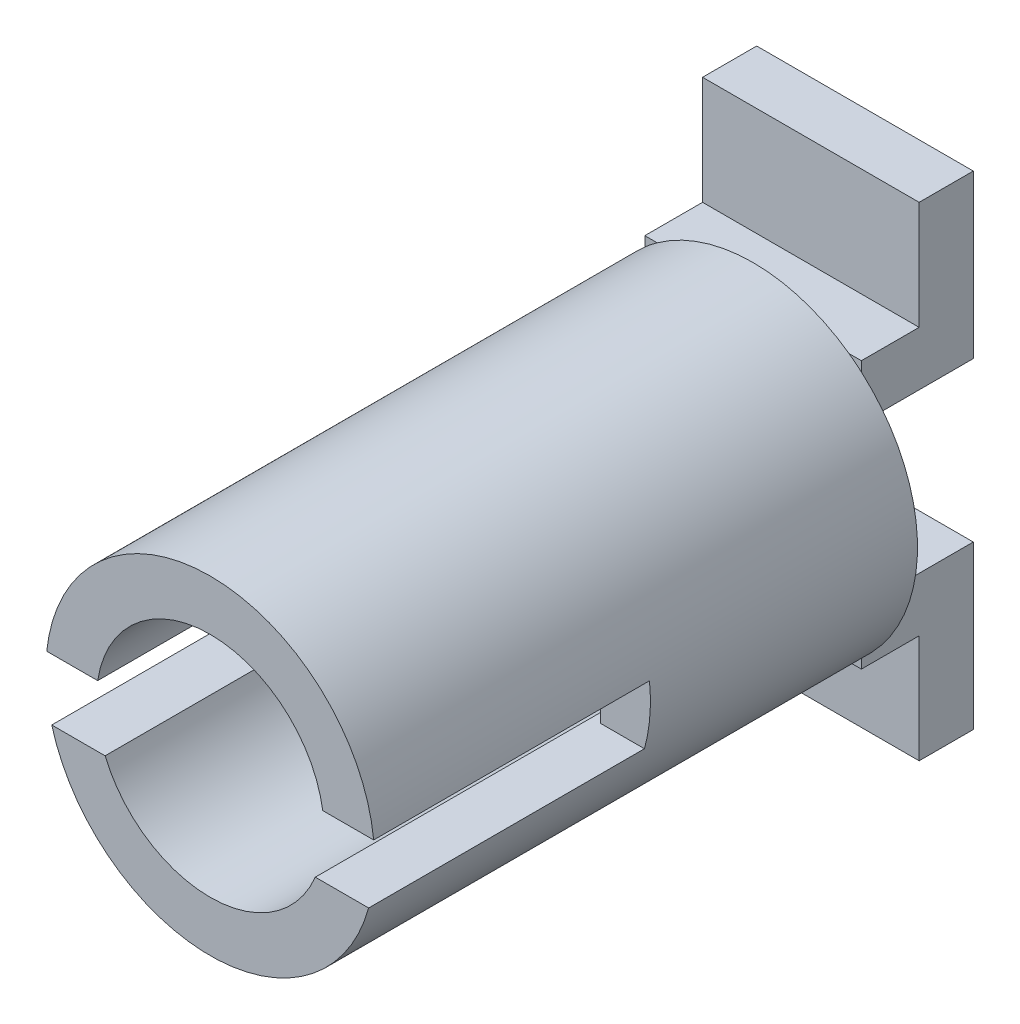
SolidWorks part; units mm, degrees
ref_plane "Front Plane" through (0, 0, 0) normal (0, 0, 1) x (1, 0, 0)
ref_plane "Top Plane" through (0, 0, 0) normal (0, 1, 0) x (1, 0, 0)
ref_plane "Right Plane" through (0, 0, 0) normal (1, 0, 0) x (0, 0, -1)
sketch "Sketch1" plane through (0, 0, 0) normal (0, 0, 1) x (1, 0, 0)
  circle A2 centre (-7.6717, 4.7989) radius 4.555
  circle A4 centre (-7.6717, 4.7989) radius 3.155
  circle A5 centre (-7.6717, 4.7989) radius 3.155
  dimension "D1" = 0.1
extrude "Boss-Extrude1" add sketch "Sketch1" along normal up to surface (7.64 mm away)
sketch "Sketch7" plane through (0, 0, 7.64) normal (0, 0, 1) x (1, 0, 0)
  line L0 (-12.2267, 4.7989) -> (-3.1167, 4.7989) construction
  circle A0 centre (-7.6717, 4.7989) radius 4.555 construction
ref_plane "Plane1" through (0, 4.7989, 0) normal (0, -1, 0) x (1, 0, 0)
sketch "Sketch2" plane through (0, 0, 0) normal (0, 0, -1) x (-1, 0, 0)
  line L4 (10.8417, 5.2839) -> (4.5017, 5.2839)
  line L5 (4.5017, 5.2839) -> (4.5017, 3.5839)
  line L6 (4.5017, 3.5839) -> (10.8417, 3.5839)
  line L7 (10.8417, 3.5839) -> (10.8417, 5.2839)
  line L8 (10.8417, 5.2839) -> (4.5017, 5.2839)
  line L9 (4.5017, 5.2839) -> (4.5017, 3.5839)
  line L10 (4.5017, 3.5839) -> (10.8417, 3.5839)
  line L11 (10.8417, 3.5839) -> (10.8417, 5.2839)
  circle A0 centre (7.6717, 4.7989) radius 3.155 construction
  circle A1 centre (7.6717, 4.7989) radius 3.155
  circle M5 centre (7.6717, 4.7989) radius 4.555
  circle M6 centre (7.6717, 4.7989) radius 3.155
  dimension "D1" = 0
extrude "Boss-Extrude2" add sketch "Sketch2" along normal up to surface (5.9 mm away) contours L11 L10 L9 L8 M5 M6 region at (-3.2455, 4.7989, 0)
sketch "Sketch3" plane through (0, 0, -5.9) normal (0, 0, -1) x (-1, 0, 0)
  line L0 (7.6717, 7.7989) -> (7.6717, 1.7989) construction
  line L1 (7.6717, 9.3539) -> (7.6717, 0.2439)
  circle A0 centre (7.6717, 4.7989) radius 4.555 construction
  circle A1 centre (7.6717, 4.7989) radius 4.555
  line M1 (10.8417, 5.2839) -> (10.8417, 3.5839)
  line M2 (10.8417, 3.5839) -> (10.5834, 3.5839)
  arc M3 (10.5834, 3.5839) -> (4.76, 3.5839) centre (7.6717, 4.7989) cw
  line M4 (4.76, 3.5839) -> (4.5017, 3.5839)
  line M5 (4.5017, 3.5839) -> (4.5017, 5.2839)
  line M6 (4.5017, 5.2839) -> (4.5542, 5.2839)
  arc M7 (4.5542, 5.2839) -> (10.7892, 5.2839) centre (7.6717, 4.7989) cw
  line M8 (10.7892, 5.2839) -> (10.8417, 5.2839)
  circle M9 centre (7.6717, 4.7989) radius 4.555
extrude "Boss-Extrude3" add sketch "Sketch3" along normal blind 1.5 contours L1 M9 M7 M8 M1 M2 M3 | L1 M7 M3 M2 M1 M8 | L1 M9 M3 M4 M5 M6 M7 region at (-10.8206, 7.9477, -5.9) region at (-7.5699, 8.6539, -5.9) region at (-9.0251, 4.7928, -5.9)
sketch "Sketch4" plane through (0, 0, -7.4) normal (0, 0, -1) x (-1, 0, 0)
  line L0 (10.6717, 4.7989) -> (4.6717, 4.7989) construction
  line L1 (7.6717, 8.4989) -> (10.6717, 8.4989)
  line L2 (7.6717, 8.4989) -> (7.6717, 1.0989)
  line L3 (7.6717, 1.0989) -> (10.6717, 1.0989)
  line L4 (10.6717, 8.4989) -> (10.6717, 1.0989)
  line L5 (7.6717, 8.4989) -> (10.6717, 1.0989) construction
  line L6 (7.6717, 1.0989) -> (10.6717, 8.4989) construction
  line L7 (7.6717, 7.9539) -> (7.6717, 1.6439) construction
  line L8 (6.1717, 6.9989) -> (6.1717, 8.4989) construction
  line L9 (4.6717, 8.4989) -> (7.6717, 8.4989)
  line L10 (4.6717, 8.4989) -> (4.6717, 1.0989)
  line L11 (4.6717, 1.0989) -> (7.6717, 1.0989)
  line L12 (7.6717, 8.4989) -> (7.6717, 1.0989)
  line L13 (4.6717, 8.4989) -> (7.6717, 1.0989) construction
  line L14 (4.6717, 1.0989) -> (7.6717, 8.4989) construction
  line L15 (10.6717, 8.4989) -> (12.1717, 8.4989)
  line L16 (10.6717, 8.4989) -> (10.6717, 6.4989)
  line L17 (10.6717, 6.4989) -> (12.1717, 6.4989)
  line L18 (12.1717, 8.4989) -> (12.1717, 6.4989)
  line L19 (10.6717, 1.0989) -> (12.1717, 1.0989)
  line L20 (10.6717, 1.0989) -> (10.6717, 3.0989)
  line L21 (10.6717, 3.0989) -> (12.1717, 3.0989)
  line L22 (12.1717, 1.0989) -> (12.1717, 3.0989)
  line L23 (4.6717, 1.0989) -> (3.1717, 1.0989)
  line L24 (4.6717, 1.0989) -> (4.6717, 3.0989)
  line L25 (4.6717, 3.0989) -> (3.1717, 3.0989)
  line L26 (3.1717, 1.0989) -> (3.1717, 3.0989)
  line L27 (4.6717, 8.4989) -> (3.1717, 8.4989)
  line L28 (4.6717, 8.4989) -> (4.6717, 6.4989)
  line L29 (4.6717, 6.4989) -> (3.1717, 6.4989)
  line L30 (3.1717, 8.4989) -> (3.1717, 6.4989)
  line L31 (4.6717, 1.0989) -> (7.6717, 1.0989)
  line L32 (4.6717, 1.0989) -> (4.6717, 2.5989)
  line L33 (4.6717, 2.5989) -> (7.6717, 2.5989)
  line L34 (7.6717, 1.0989) -> (7.6717, 2.5989)
  line L35 (4.6717, 8.4989) -> (7.6717, 8.4989)
  line L36 (4.6717, 8.4989) -> (4.6717, 6.9989)
  line L37 (4.6717, 6.9989) -> (7.6717, 6.9989)
  line L38 (7.6717, 8.4989) -> (7.6717, 6.9989)
  line L39 (6.1717, 2.5989) -> (6.1717, 1.0989) construction
  point P0 (9.1717, 4.7989)
  point P9 (6.1717, 4.7989)
  circle M18 centre (7.6717, 4.7989) radius 4.555
  line M19 (7.6717, 7.9539) -> (7.6717, 1.6439)
  arc M44 (4.5542, 5.2839) -> (7.6717, 7.9539) centre (7.6717, 4.7989) cw
  arc M45 (7.6717, 1.6439) -> (4.76, 3.5839) centre (7.6717, 4.7989) cw
  dimension "D1" = 3
  dimension "D2" = 7.4
  dimension "D3" = 3.4
  dimension "D4" = 1.5
extrude "Boss-Extrude4" add sketch "Sketch4" along normal blind 3.1 contours L4 L1 L12 L3 M18 M19 | L10 L37 L9 M19 | L33 L24 L11 L12 | L4 L1 M18 | L4 L3 M18 | L9 L10 M18 | L10 L11 M18 | L33 L12 M45 | L37 M44 M19 region at (-9.166, 4.7989, -7.4) region at (-5.8754, 7.921, -7.4) region at (-10.5592, 8.4096, -7.4) region at (-6.8035, 7.3863, -7.4) region at (-4.7842, 8.4096, -7.4) region at (-6.8035, 2.2115, -7.4) region at (-5.8754, 1.6768, -7.4) region at (-10.5592, 1.1882, -7.4) region at (-4.7842, 1.1882, -7.4)
sketch "Sketch5" plane through (0, 8.4989, 0) normal (0, 1, 0) x (1, 0, 0)
  line L0 (-10.6717, 10.5) -> (-10.6717, 7.4) construction
  line L1 (-10.6717, 9) -> (-4.6717, 9)
  line L2 (-10.6717, 9) -> (-10.6717, 10.5)
  line L3 (-10.6717, 10.5) -> (-4.6717, 10.5)
  line L4 (-4.6717, 9) -> (-4.6717, 10.5)
  dimension "D1" = 1.5
extrude "Boss-Extrude5" add sketch "Sketch5" along normal blind 3
mirror "Mirror1" about plane through (0, 4.7989, 0) normal (0, -1, 0) of "Boss-Extrude5"
sketch "Sketch8" plane through (0, 0, 7.64) normal (0, 0, 1) x (1, 0, 0)
  line L0 (-10.8417, 3.5839) -> (-10.8417, 5.2839) construction
  line L1 (-4.5017, 5.2839) -> (-4.5017, 3.5839) construction
  line L2 (-10.8417, 3.5839) -> (-10.8417, 5.2839) construction
  line L3 (-4.5017, 5.2839) -> (-4.5017, 3.5839) construction
  line L4 (-4.5017, 5.2839) -> (-10.8417, 5.2839)
  line L5 (-10.8417, 3.5839) -> (-4.5017, 3.5839)
  line L6 (-12.2267, 3.5839) -> (-12.2267, 5.2839)
  line L7 (-3.1167, 3.5839) -> (-3.1167, 5.2839)
  line L8 (-3.1167, 3.5839) -> (-4.5017, 3.5839)
  line L9 (-10.8417, 3.5839) -> (-12.2267, 3.5839)
  line L10 (-12.2267, 5.2839) -> (-10.8417, 5.2839)
  line L11 (-3.1167, 5.2839) -> (-4.5017, 5.2839)
  circle A0 centre (-7.6717, 4.7989) radius 4.555 construction
extrude "Cut-Extrude1" cut sketch "Sketch8" against normal up to surface (7.64 mm away) up to face at (-10.7934, 4.4303, 0)
equation "\"D3@Sketch4\"=3.00mm+.2*2"
